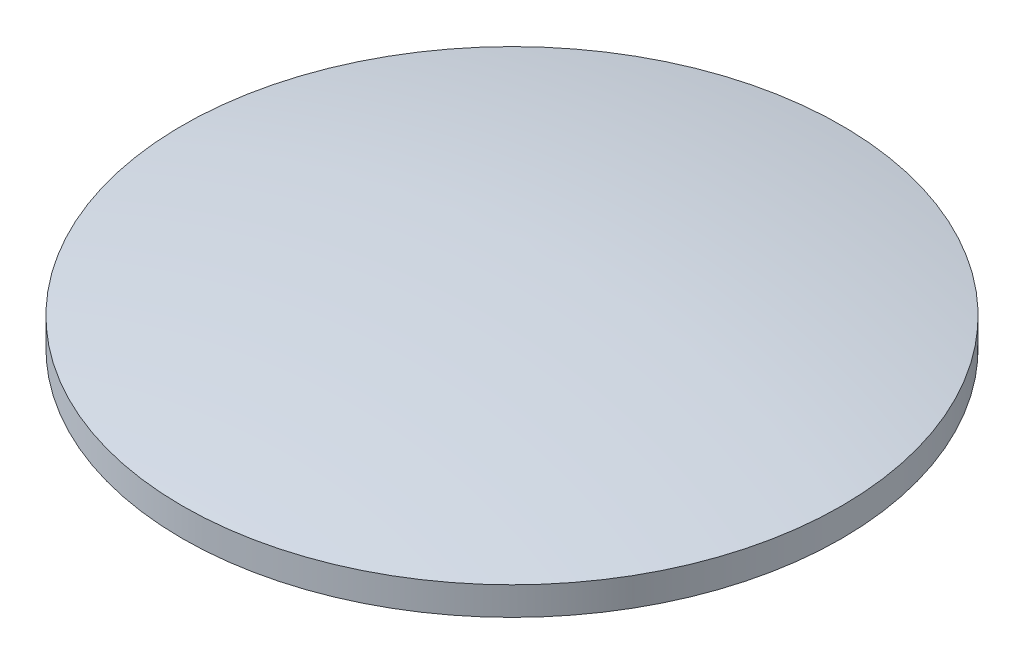
SolidWorks part; units mm, degrees
ref_plane "Front" through (0, 0, 0) normal (0, 0, 1) x (1, 0, 0)
ref_plane "Top" through (0, 0, 0) normal (0, 1, 0) x (1, 0, 0)
ref_plane "Right" through (0, 0, 0) normal (1, 0, 0) x (0, 0, -1)
sketch "Sketch1" plane through (0, 0, 0) normal (0, 0, 1) x (1, 0, 0)
  line L0 (0, 5) -> (0, -5)
  line L1 (35, 1.5) -> (35, -1.5)
  line L3 (0, 38.8712) -> (0, -46.0409) construction
  arc A0 (0, 5) -> (35, 1.5) centre (0, -171.75) cw
  arc A1 (0, -5) -> (35, -1.5) centre (0, 171.75) ccw
  dimension "D1" = 10
  dimension "D2" = 5
  dimension "D3" = 3
  dimension "D4" = 70
revolve "Revolve7" add sketch "Sketch1" angle 360 about L3
ref_axis "Axis1" through (80.9, 0, 0) along (-1, 0, 0)
ref_axis "Axis2" through (0, 0, -80.9) along (0, 0, 1)
